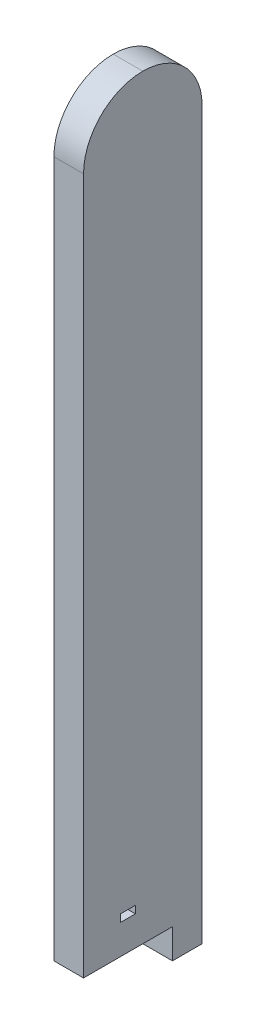
SolidWorks part; units mm, degrees
ref_plane "Front Plane" through (0, 0, 0) normal (0, 0, 1) x (1, 0, 0)
ref_plane "Top Plane" through (0, 0, 0) normal (0, 1, 0) x (1, 0, 0)
ref_plane "Right Plane" through (0, 0, 0) normal (1, 0, 0) x (0, 0, -1)
sketch "Sketch1" plane through (0, 0, 0) normal (1, 0, 0) x (0, 0, -1)
  line L0 (12.7, -69.5376) -> (12.7, -155.575)
  line L1 (-12.7, 12.7) -> (12.7, 12.7)
  line L2 (-12.7, 12.7) -> (-12.7, -149.225)
  line L3 (-12.7, -149.225) -> (6.35, -149.225)
  line L4 (12.7, 12.7) -> (12.7, -69.5376)
  line L7 (12.7, -155.575) -> (6.35, -155.575)
  line L8 (6.35, -155.575) -> (6.35, -149.225)
  line L9 (4.503, -152.4) -> (-49995.497, -152.4) construction
  line L11 (-12.7, 12.7) -> (0, 0) construction
  line L12 (0, 0) -> (12.7, 12.7) construction
  point P0 (0, 0)
  point P11 (6.35, -152.4)
  dimension "D1" = 25.4
  dimension "D2" = 6.35
  dimension "D3" = 6.35
  dimension "D4" = 152.4
extrude "Boss-Extrude1" add sketch "Sketch1" along normal mid plane 6.35
fillet "Fillet1" radius 12.7 2 edges at (0, 12.7, -12.7) (0, 12.7, 12.7)
sketch "Sketch2" plane through (3.175, 0, 0) normal (1, 0, 0) x (0, 0, -1)
  line L1 (-4.7625, -142.875) -> (-1.5875, -142.875)
  line L2 (-4.7625, -142.875) -> (-4.7625, -141.2875)
  line L3 (-4.7625, -141.2875) -> (-1.5875, -141.2875)
  line L4 (-1.5875, -142.875) -> (-1.5875, -141.2875)
  line L5 (-4.7625, -142.875) -> (-1.5875, -141.2875) construction
  line L6 (-4.7625, -141.2875) -> (-1.5875, -142.875) construction
  line L7 (-3.175, -149.225) -> (-3.175, -142.0812) construction
  line L8 (-12.7, -149.225) -> (6.35, -149.225) construction
  point P0 (-3.175, -142.0812)
  dimension "D1" = 6.35
  dimension "D2" = 1.5875
  dimension "D3" = 3.175
extrude "Cable-tie hole" cut sketch "Sketch2" against normal through all
